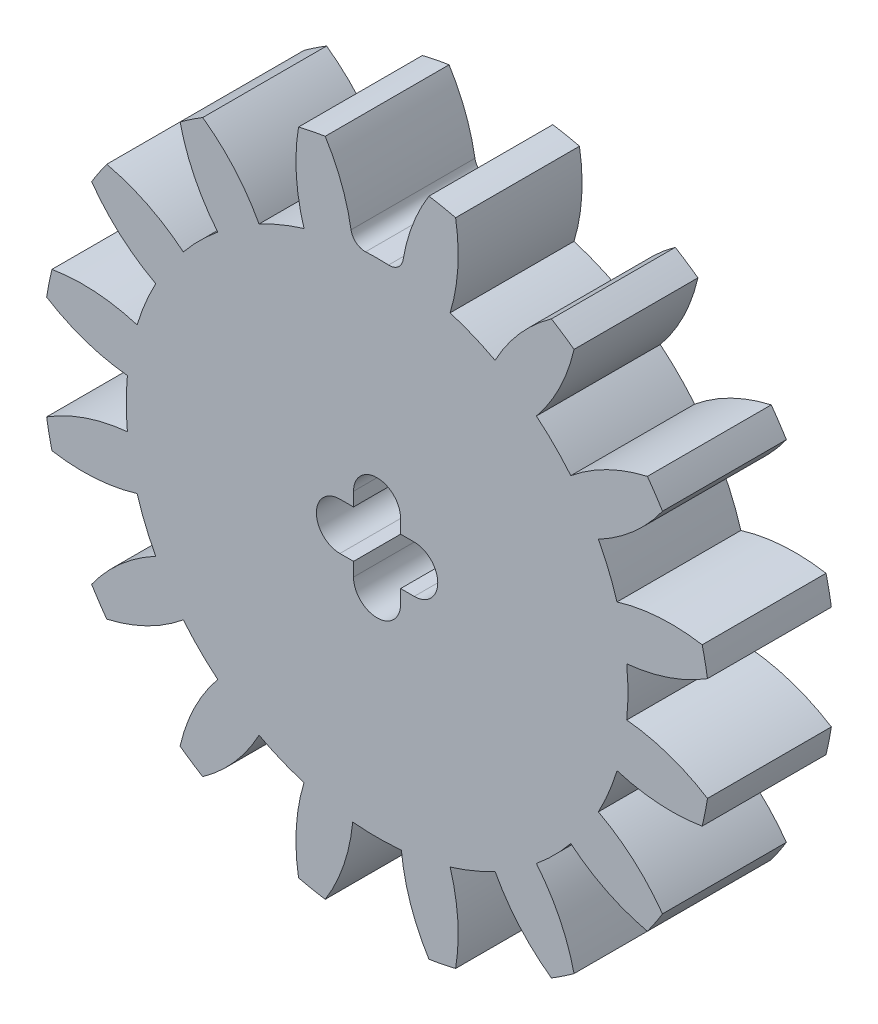
SolidWorks part; units mm, degrees
ref_plane "Front Plane" through (0, 0, 0) normal (0, 0, 1) x (1, 0, 0)
ref_plane "Top Plane" through (0, 0, 0) normal (0, 1, 0) x (1, 0, 0)
ref_plane "Right Plane" through (0, 0, 0) normal (1, 0, 0) x (0, 0, -1)
sketch "Sketch1" plane through (0, 0, 0) normal (0, 0, 1) x (1, 0, 0)
  line L0 (0, -1.5) -> (0, 1.5) construction
  line L1 (-0.95, -1.5) -> (-0.95, 1.5)
  line L2 (0.95, -1.5) -> (0.95, 1.5)
  line L3 (-1.5, 0) -> (1.5, 0) construction
  line L4 (-1.5, 0.95) -> (1.5, 0.95)
  line L5 (-1.5, -0.95) -> (1.5, -0.95)
  circle A0 centre (0, 0) radius 13.5
  arc A2 (-0.95, -1.5) -> (0.95, -1.5) centre (0, -1.5) ccw
  arc A3 (0.95, 1.5) -> (-0.95, 1.5) centre (0, 1.5) ccw
  arc A4 (-1.5, 0.95) -> (-1.5, -0.95) centre (-1.5, 0) ccw
  arc A5 (1.5, -0.95) -> (1.5, 0.95) centre (1.5, 0) ccw
  point P5 (0, 0)
  point P11 (0, 0)
  dimension "D2" = 27
  dimension "D1" = 4.9
  dimension "D3" = 4.9
  dimension "D4" = 1.9
  dimension "D5" = 1.9
extrude "Boss-Extrude1" add sketch "Sketch1" along normal mid plane 5 contours A0 A5 L5 L2 A2 L1 A4 L4 A3 region at (-13.1182, 0, 0)
sketch "Sketch2" plane through (0, 0, 0) normal (0, 0, 1) x (1, 0, 0)
  line L0 (0, 0) -> (0, 13.5) construction
  line L1 (0, 0) -> (-0.9822, 10.0772) construction
  line L2 (0, 8.0719) -> (-4.2467, 19.7397) construction
  arc A0 (1.3999, 11.9181) -> (-1.3999, 11.9181) centre (0, 0) ccw construction
  arc A1 (0.9822, 10.0772) -> (-0.9822, 10.0772) centre (0, 0) ccw
  arc A3 (2.0928, 13.3368) -> (-2.0928, 13.3368) centre (0, 0) ccw
  arc A4 (-0.9822, 10.0772) -> (-2.0928, 13.3368) centre (-8.4601, 9.3484) ccw
  arc A5 (0.9822, 10.0772) -> (2.0928, 13.3368) centre (8.4601, 9.3484) cw
  circle A6 centre (0, 0) radius 13.5 construction
  dimension "D1" = 24
  dimension "D2" = 3.375
  dimension "D3" = 20
  dimension "D4" = 2.8062
extrude "Cut-Extrude1" cut sketch "Sketch2" against normal through all both and the other way through all
fillet "Fillet1" radius 0.57 2 edges at (0.9822, 10.0772, 0) (-0.9822, 10.0772, 0)
pattern_circular "CirPattern3" count 16 over 360 about axis through (0, 0, 2.5) along (0, 0, -1) of "Cut-Extrude1"
equation "\"Module\"= 1.5"
equation "\"Pressure Angle\"= 20"
equation "\"Bore\"= 2"
equation "\"NumTeeth\"= 16"
equation "\"D2@Sketch1\"=(\"NumTeeth\"+2)*\"Module\""
equation "\"D1@Sketch2\"=\"NumTeeth\"*\"Module\""
equation "\"ToothDepth\"= IIF ( \"Module\" < 1.25 , 2.4 * \"Module\" , 2.25 * \"Module\" )"
equation "\"D2@Sketch2\"=\"ToothDepth\""
equation "\"D3@Sketch2\"=\"Pressure Angle\""
equation "\"D4@Sketch2\"=((\"Module\"*PI)/2)+0.3*\"Module\""
equation "\"D1@Fillet1\"=\"Module\"*0.38"
equation "\"D1@CirPattern3\"=\"NumTeeth\""
equation "\"D3@Sketch1\"=\"D1@Sketch1\""
equation "\"D5@Sketch1\"=\"D4@Sketch1\""
